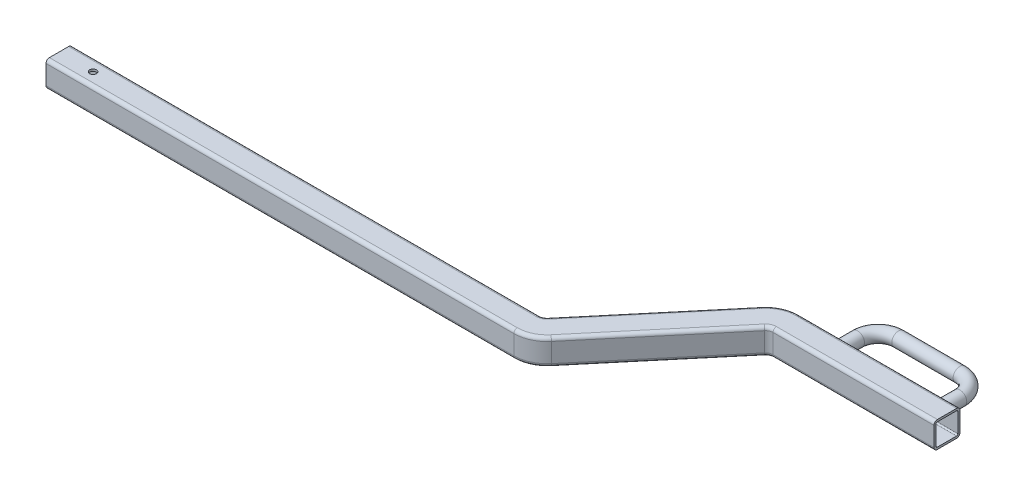
SolidWorks part; units mm, degrees
material "5052-H38, Rod (SS)"
ref_plane "Front Plane" through (0, 0, 0) normal (0, 0, 1) x (1, 0, 0)
ref_plane "Top Plane" through (0, 0, 0) normal (0, 1, 0) x (1, 0, 0)
ref_plane "Right Plane" through (0, 0, 0) normal (1, 0, 0) x (0, 0, -1)
sketch "Sketch2" plane through (0, 0, 0) normal (1, 0, 0) x (0, 0, -1)
  line L1 (-14.05, -19.05) -> (14.05, -19.05)
  line L2 (-19.05, -14.05) -> (-19.05, 14.05)
  line L3 (-14.05, 19.05) -> (14.05, 19.05)
  line L4 (19.05, -14.05) -> (19.05, 14.05)
  line L5 (-19.05, -19.05) -> (19.05, 19.05) construction
  line L6 (-19.05, 19.05) -> (19.05, -19.05) construction
  arc A0 (19.05, -14.05) -> (14.05, -19.05) centre (14.05, -14.05) cw
  arc A1 (-14.05, -19.05) -> (-19.05, -14.05) centre (-14.05, -14.05) cw
  arc A2 (-19.05, 14.05) -> (-14.05, 19.05) centre (-14.05, 14.05) cw
  arc A3 (14.05, 19.05) -> (19.05, 14.05) centre (14.05, 14.05) cw
  point P0 (0, 0)
  dimension "D3" = 5
  dimension "D1" = 38.1
  dimension "D2" = 38.1
sketch3d "3DSketch2"
  line L0 (708.9921, 0, -10.7164) -> (851.7048, 0, -180.7947)
  line L1 (874.6861, 0, -191.5111) -> (1110.6969, 0, -191.5111)
  line L3 (0, 0, 0) -> (686.0108, 0, 0)
  line L4 (700, 0, 0) -> (828.2254, 0, 0) construction
  arc A0 (851.7048, 0, -180.7947) -> (874.6861, 0, -191.5111) centre (874.6861, 0, -161.5111) ccw
  arc A1 (686.0108, 0, 0) -> (708.9921, 0, -10.7164) centre (686.0108, 0, -30) ccw
  point P9 (860.6969, 0, -191.5111)
  point P10 (874.6861, -30, -161.5111)
  point P13 (700, 0, 0)
  point P15 (686.0108, 30, -30)
  dimension "D5" = 30
  dimension "D6" = 30
  dimension "D1" = 700
  dimension "D2" = 250
  dimension "D3" = 130
  dimension "D4" = 250
sweep "Sweep-Thin3" add profiles "Sketch2" path "3DSketch2" parameters "D1"=3
sketch "Sketch21" plane through (0, 0, 0) normal (0, 1, 0) x (1, 0, 0)
  line L0 (0, 0) -> (686.0108, 0) construction
  circle A0 centre (50, 0) radius 5
  dimension "D1" = 10
  dimension "D2" = 50
extrude "Cut-Extrude3" cut sketch "Sketch21" against normal through all both and the other way through all
sketch "Sketch22" [suppressed] plane through (0, 0, 0) normal (0, 0, 1) x (1, 0, 0)
ref_plane "Plane1" [suppressed] through (0, -210, 0) normal (0, 1, 0) x (1, 0, 0)
ref_plane "Plane2" through (0, 0, 0) normal (0, -1, 0) x (1, 0, 0)
sketch "Sketch24" plane through (0, 0, -210.5611) normal (0, 0, -1) x (-1, 0, 0)
  line L0 (-874.6861, 0) -> (-1110.6969, 0) construction
  line L1 (-874.6861, -14.05) -> (-874.6861, 14.05) construction
  line L2 (-1110.6969, -14.05) -> (-1110.6969, 14.05) construction
sketch "Sketch25" plane through (0, 0, 0) normal (0, -1, 0) x (1, 0, 0)
  line L0 (874.6861, -210.5611) -> (1110.6969, -210.5611) construction
  line L1 (1080.6969, -210.5611) -> (1080.6969, -240.5611)
  line L2 (1050.6969, -270.5611) -> (960.6969, -270.5611)
  line L3 (930.6969, -240.5611) -> (930.6969, -210.5611)
  arc A0 (1080.6969, -240.5611) -> (1050.6969, -270.5611) centre (1050.6969, -240.5611) cw
  arc A1 (960.6969, -270.5611) -> (930.6969, -240.5611) centre (960.6969, -240.5611) cw
  point P10 (1080.6969, -270.5611)
  point P13 (930.6969, -270.5611)
  dimension "D3" = 30
  dimension "D1" = 150
  dimension "D2" = 60
  dimension "D4" = 30
sweep "Sweep-Thin4" add path "Sketch25" circular profile diameter 20 parameters "D1"=3, "D3"=20
